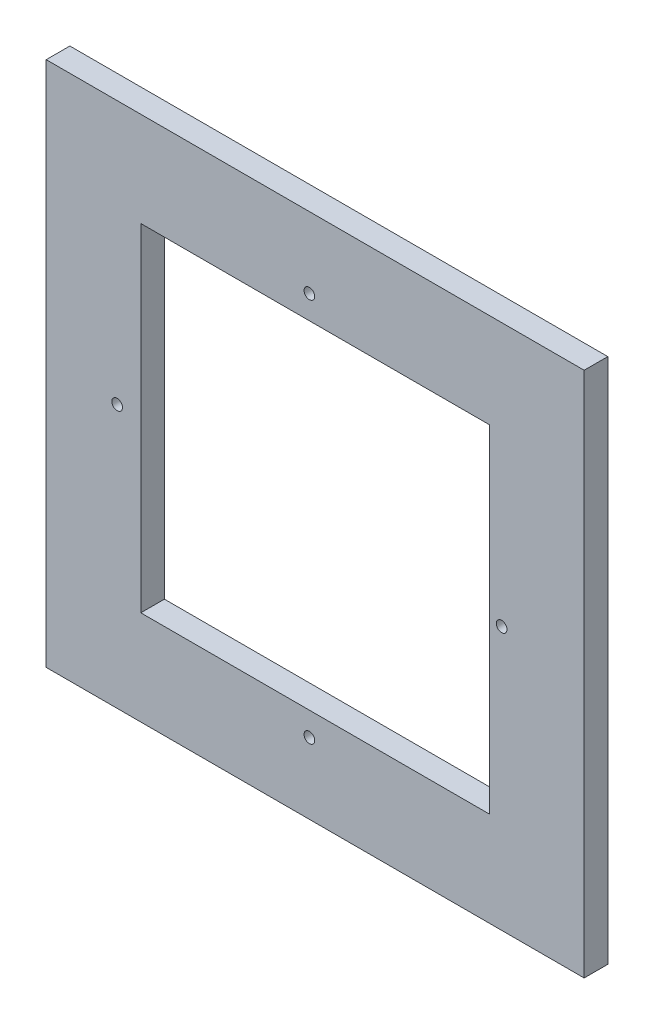
SolidWorks part; units mm, degrees
ref_plane "Front Plane" through (0, 0, 0) normal (0, 0, 1) x (1, 0, 0)
ref_plane "Top Plane" through (0, 0, 0) normal (0, 1, 0) x (1, 0, 0)
ref_plane "Right Plane" through (0, 0, 0) normal (1, 0, 0) x (0, 0, -1)
sketch "Sketch1" plane through (0, 0, 0) normal (0, 0, 1) x (1, 0, 0)
  line L0 (0, 0) -> (0, 51.6255) construction
  line L1 (0, 0) -> (0, -51.6255) construction
  line L3 (-70.6755, 45.2755) -> (73.7859, 45.2755)
  line L5 (-70.6755, 70.6755) -> (73.7859, 70.6755)
  line L7 (-70.6755, 45.2755) -> (-70.6755, 70.6755)
  line L8 (-70.6755, 45.2755) -> (-45.2755, 45.2755)
  line L9 (-70.6755, -70.6755) -> (73.7859, -70.6755)
  line L11 (-70.6755, -45.2755) -> (73.7859, -45.2755)
  line L13 (-70.6755, 45.2755) -> (-70.6755, -45.2755)
  line L14 (-70.6755, -45.2755) -> (-45.2755, -45.2755)
  line L15 (-45.2755, 45.2755) -> (-45.2755, -45.2755)
  line L16 (48.3859, 45.2755) -> (73.7859, 45.2755)
  line L17 (48.3859, 45.2755) -> (48.3859, -45.2755)
  line L18 (48.3859, -45.2755) -> (73.7859, -45.2755)
  line L19 (73.7859, 45.2755) -> (73.7859, -45.2755)
  line L20 (73.7859, 70.6755) -> (73.7859, 45.2755)
  line L21 (-70.6755, -45.2755) -> (-70.6755, -70.6755)
  line L22 (73.7859, -45.2755) -> (73.7859, -70.6755)
  line L23 (-70.6755, 70.6755) -> (73.7859, 70.6755)
  line L24 (-70.6755, 70.6755) -> (-70.6755, 45.2755)
  line L25 (-70.6755, 45.2755) -> (73.7859, 45.2755)
  line L26 (73.7859, 70.6755) -> (73.7859, 45.2755)
  line L28 (-70.6755, -45.2755) -> (73.7859, -45.2755)
  line L29 (-70.6755, -45.2755) -> (-70.6755, -70.6755)
  line L30 (-70.6755, -70.6755) -> (73.7859, -70.6755)
  line L31 (73.7859, -45.2755) -> (73.7859, -70.6755)
  circle A1 centre (0, 51.6255) radius 1.4351
  circle A3 centre (0, -51.6255) radius 1.4351
  circle A5 centre (-51.6255, 0) radius 1.4351 [skipped]
  circle A6 centre (51.6255, 0) radius 1.4351 [skipped]
  circle A7 centre (0, 0) radius 51.6255 construction
  circle A8 centre (-51.6255, 0) radius 1.4351
  circle A9 centre (51.6255, 0) radius 1.4351
  dimension "D1" = 51.6255
  dimension "D3" = 2.8702
  dimension "D9" = 45.2755
  dimension "D10" = 2.8702
  dimension "D11" = 2.8702
  dimension "D2" = 51.6255
  dimension "D8" = 45.2755
  dimension "D12" = 25.4
  dimension "D13" = 6.35
  dimension "D14" = 25.4
  dimension "D15" = 48.3859
  dimension "D4" = 4
extrude "Boss-Extrude4" add sketch "Sketch1" along normal blind 6.35 contours L20 L5 L7 L3 A1 | L15 L3 L13 L11 A8 | L19 L3 L17 L11 A9 | L22 L11 L21 L9 A3 region at (1.5579, 57.9867, 0) region at (-57.9934, 0, 0) region at (1.5579, -57.9867, 0) region at (61.1125, 0, 0)
